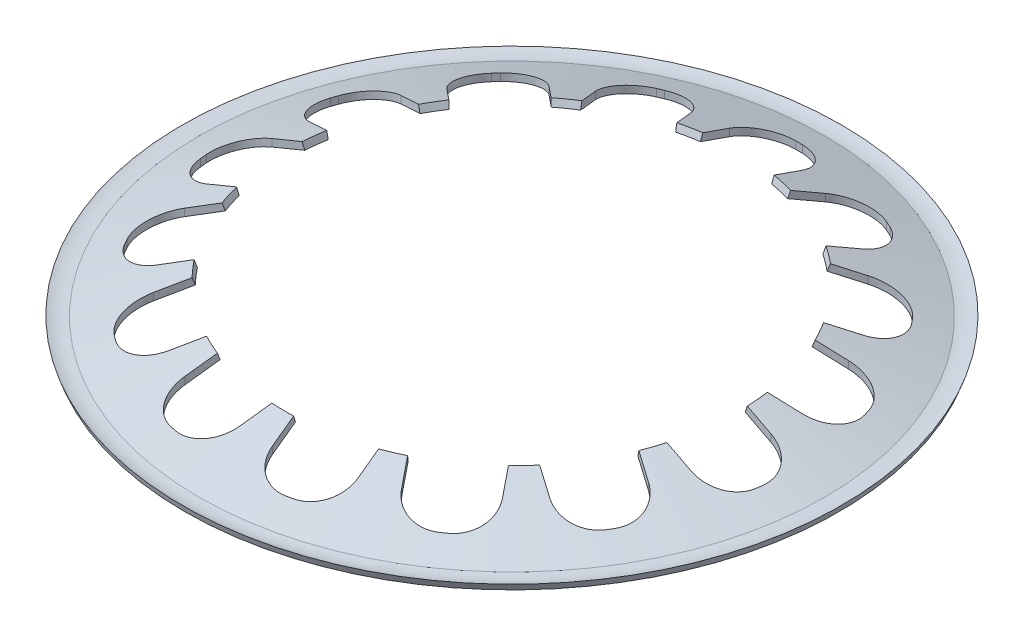
SolidWorks part; units mm, degrees
ref_plane "Plano frontal" through (0, 0, 0) normal (0, 0, 1) x (1, 0, 0)
ref_plane "Plano superior" through (0, 0, 0) normal (0, 1, 0) x (1, 0, 0)
ref_plane "Plano direito" through (0, 0, 0) normal (1, 0, 0) x (0, 0, -1)
sketch "Esboço1" plane through (0, 0, 0) normal (0, 0, 1) x (1, 0, 0)
  line L0 (0, -72.5644) -> (0, 61.8053) construction
  line L1 (40.25, 8.8426) -> (56.25, 3.1611)
  line L2 (58.8317, 3.5206) -> (59.25, 4.6985)
  line L3 (56.25, 4.4875) -> (40.6683, 10.0206)
  line L4 (40.6683, 10.0206) -> (40.25, 8.8426)
  arc A0 (56.25, 3.1611) -> (58.8317, 3.5206) centre (57.0193, 7.0864) ccw
  arc A1 (59.25, 4.6985) -> (56.25, 4.4875) centre (57.2704, 11.4128) cw
  point P13 (44.8894, 9.9657)
  dimension "D6" = 7
  dimension "D7" = 4
  dimension "D1" = 59.25
  dimension "D2" = 19
  dimension "D3" = 1.25
  dimension "D4" = 1.25
  dimension "D5" = 6.5
  dimension "D8" = 16
revolve "Revolução1" add sketch "Esboço1" angle 360 about L0
sketch "Esboço2" plane through (0, 0, 0) normal (0, 1, 0) x (1, 0, 0)
  line L0 (0, 0) -> (0, 25.5375) construction
  line L1 (-5.9196, 20.5713) -> (7.0804, 20.5713)
  line L2 (-5.9196, 20.5713) -> (-5.9196, 44.9999)
  line L3 (7.0804, 20.5713) -> (7.0804, 44.987)
  line L4 (2.9592, 21.2006) -> (14.8353, 15.913)
  line L5 (2.9592, 21.2006) -> (12.8953, 43.5172)
  line L6 (14.8353, 15.913) -> (24.7661, 38.2179)
  line L7 (0, 0) -> (10.387, 23.3297) construction
  line L8 (11.3265, 18.1641) -> (20.0252, 8.5032)
  line L9 (11.3265, 18.1641) -> (29.4804, 34.51)
  line L10 (20.0252, 8.5032) -> (38.1696, 24.8405)
  line L11 (0, 0) -> (18.9781, 17.0879) construction
  line L12 (17.7352, 11.9868) -> (21.7524, -0.3769)
  line L13 (17.7352, 11.9868) -> (40.9682, 19.5357)
  line L14 (21.7524, -0.3769) -> (44.9732, 7.1679)
  line L15 (0, 0) -> (24.2876, 7.8915) construction
  line L16 (21.0774, 3.7369) -> (19.7185, -9.1919)
  line L17 (21.0774, 3.7369) -> (45.3722, 1.1834)
  line L18 (19.7185, -9.1919) -> (44.0005, -11.744)
  line L19 (0, 0) -> (25.3976, -2.6694) construction
  line L20 (20.7751, -5.1591) -> (14.2751, -16.4174)
  line L21 (20.7751, -5.1591) -> (41.9309, -17.3734)
  line L22 (14.2751, -16.4174) -> (35.4197, -28.6253)
  line L23 (0, 0) -> (22.1161, -12.7688) construction
  line L24 (16.8806, -13.1631) -> (6.3634, -20.8043)
  line L25 (16.8806, -13.1631) -> (31.2394, -32.9262)
  line L26 (6.3634, -20.8043) -> (20.7146, -40.557)
  line L27 (0, 0) -> (15.0106, -20.6603) construction
  line L28 (10.0673, -18.891) -> (-2.6486, -21.5939)
  line L29 (10.0673, -18.891) -> (15.1463, -42.7858)
  line L30 (-2.6486, -21.5939) -> (2.4277, -45.476)
  line L31 (0, 0) -> (5.3096, -24.9795) construction
  line L32 (1.5133, -21.3526) -> (-11.2027, -18.6497)
  line L33 (1.5133, -21.3526) -> (-3.5657, -45.2473)
  line L34 (-11.2027, -18.6497) -> (-16.279, -42.5319)
  line L35 (0, 0) -> (-5.3096, -24.9795) construction
  line L36 (-7.3024, -20.122) -> (-17.8197, -12.4808)
  line L37 (-7.3024, -20.122) -> (-21.6612, -39.8852)
  line L38 (-17.8197, -12.4808) -> (-32.1708, -32.2335)
  line L39 (0, 0) -> (-15.0106, -20.6603) construction
  line L40 (-14.8555, -15.4122) -> (-21.3555, -4.1539)
  line L41 (-14.8555, -15.4122) -> (-36.0113, -27.6265)
  line L42 (-21.3555, -4.1539) -> (-42.5001, -16.3617)
  line L43 (0, 0) -> (-22.1161, -12.7688) construction
  line L44 (-19.8399, -8.0375) -> (-21.1987, 4.8913)
  line L45 (-19.8399, -8.0375) -> (-44.1346, -10.591)
  line L46 (-21.1987, 4.8913) -> (-50.9695, 1.7622)
  line L47 (0, 0) -> (-25.3976, -2.6694) construction
  line L48 (-21.3938, 0.727) -> (-17.3765, 13.0907)
  line L49 (-21.3938, 0.727) -> (-44.6267, 8.2758)
  line L50 (-17.3765, 13.0907) -> (-40.5973, 20.6356)
  line L51 (0, 0) -> (-24.2876, 7.8915) construction
  line L52 (-19.2485, 9.3658) -> (-10.5498, 19.0266)
  line L53 (-19.2485, 9.3658) -> (-37.4025, 25.7117)
  line L54 (-10.5498, 19.0266) -> (-28.6942, 35.3639)
  line L55 (0, 0) -> (-18.9781, 17.0879) construction
  line L56 (-13.775, 16.3851) -> (-1.8989, 21.6727)
  line L57 (-13.775, 16.3851) -> (-23.711, 38.7017)
  line L58 (-1.8989, 21.6727) -> (-11.8296, 43.9775)
  line L59 (0, 0) -> (-10.387, 23.3297) construction
  arc A0 (20.8267, 46.5537) -> (21.8561, 46.0794) centre (0, 0) cw
  arc A1 (0.0911, 50.9999) -> (1.2244, 50.9853) centre (0, 0) cw
  arc A2 (37.9613, 34.0579) -> (38.7087, 33.2059) centre (0, 0) cw
  arc A3 (48.5319, 15.6732) -> (48.8683, 14.5908) centre (0, 0) cw
  arc A4 (50.711, -5.4215) -> (50.578, -6.5471) centre (0, 0) cw
  arc A5 (44.1217, -25.5788) -> (43.5424, -26.553) centre (0, 0) cw
  arc A6 (29.9033, -41.3133) -> (28.9778, -41.9677) centre (0, 0) cw
  arc A7 (10.5144, -49.9044) -> (9.4028, -50.1257) centre (0, 0) cw
  arc A8 (-10.6926, -49.8665) -> (-11.7981, -49.6166) centre (0, 0) cw
  arc A9 (-30.0507, -41.2063) -> (-30.959, -40.5283) centre (0, 0) cw
  arc A10 (-44.2128, -25.4211) -> (-44.7668, -24.4323) centre (0, 0) cw
  arc A11 (-50.7301, -5.2404) -> (-50.9695, 1.7622) centre (0, 0) cw
  arc A12 (-48.4757, 15.8465) -> (-48.1115, 16.9198) centre (0, 0) cw
  arc A13 (-37.8394, 34.1933) -> (-37.0702, 35.0257) centre (0, 0) cw
  arc A14 (-20.6603, 46.6278) -> (-19.619, 47.0754) centre (0, 0) cw
  arc A15 (-16.279, -42.5319) -> (-11.7981, -49.6166) centre (-10.4101, -43.7793) ccw
  arc A16 (-3.5657, -45.2473) -> (-10.6926, -49.8665) centre (-9.4346, -43.9999) cw
  arc A17 (15.1463, -42.7858) -> (10.5144, -49.9044) centre (9.2774, -44.0333) cw
  arc A18 (2.4277, -45.476) -> (9.4028, -50.1257) centre (8.2966, -44.2286) ccw
  arc A19 (31.2394, -32.9262) -> (29.9033, -41.3133) centre (26.3853, -36.4529) cw
  arc A20 (20.7146, -40.557) -> (28.9778, -41.9677) centre (25.5687, -37.0303) ccw
  arc A21 (41.9309, -17.3734) -> (44.1217, -25.5788) centre (38.9309, -22.5696) cw
  arc A22 (35.4197, -28.6253) -> (43.5424, -26.553) centre (38.4197, -23.4291) ccw
  arc A23 (44.0005, -11.744) -> (50.578, -6.5471) centre (44.6277, -5.7769) ccw
  arc A24 (45.3722, 1.1834) -> (50.711, -5.4215) centre (44.745, -4.7837) cw
  arc A25 (44.9732, 7.1679) -> (48.8683, 14.5908) centre (43.1191, 12.8743) ccw
  arc A26 (40.9682, 19.5357) -> (48.5319, 15.6732) centre (42.8223, 13.8293) cw
  arc A27 (38.1696, 24.8405) -> (38.7087, 33.2059) centre (34.1548, 29.2993) ccw
  arc A28 (29.4804, 34.51) -> (37.9613, 34.0579) centre (33.4952, 30.0511) cw
  arc A29 (24.7661, 38.2179) -> (21.8561, 46.0794) centre (19.2848, 40.6583) ccw
  arc A30 (12.8953, 43.5172) -> (20.8267, 46.5537) centre (18.3765, 41.0768) cw
  arc A31 (7.0804, 44.987) -> (1.2244, 50.9853) centre (1.0804, 44.987) ccw
  arc A32 (-5.9196, 44.9999) -> (0.0911, 50.9999) centre (0.0804, 44.9999) cw
  arc A33 (-11.8296, 43.9775) -> (-19.619, 47.0754) centre (-17.3109, 41.5371) ccw
  arc A34 (-23.711, 38.7017) -> (-20.6603, 46.6278) centre (-18.2297, 41.1422) cw
  arc A35 (-28.6942, 35.3639) -> (-37.0702, 35.0257) centre (-32.709, 30.9051) ccw
  arc A36 (-37.4025, 25.7117) -> (-37.8394, 34.1933) centre (-33.3877, 30.1705) cw
  arc A37 (-40.5973, 20.6356) -> (-48.1115, 16.9198) centre (-42.4514, 14.9292) ccw
  arc A38 (-44.6267, 8.2758) -> (-48.4757, 15.8465) centre (-42.7726, 13.9822) cw
  arc A39 (-44.1346, -10.591) -> (-50.7301, -5.2404) centre (-44.7618, -4.6239) cw
  arc A40 (-42.5001, -16.3617) -> (-44.7668, -24.4323) centre (-39.5001, -21.5579) ccw
  arc A41 (-36.0113, -27.6265) -> (-44.2128, -25.4211) centre (-39.0113, -22.4304) cw
  arc A42 (-32.1708, -32.2335) -> (-30.959, -40.5283) centre (-27.3167, -35.7603) ccw
  arc A43 (-21.6612, -39.8852) -> (-30.0507, -41.2063) centre (-26.5153, -36.3585) cw
  point P80 (0, 0)
  dimension "D2" = 15
  dimension "D3" = 6
  dimension "D1" = 13
extrude "Corte-extrusão2" cut sketch "Esboço2" along normal through all contours A7 L29 L26 L24 L28 L32 L33 L30 | A6 L25 L22 L20 L24 L28 L29 L26 | A5 L21 L18 L16 L20 L24 L25 L22 | A4 L17 L14 L12 L16 L20 L21 L18 | A3 L13 L10 L8 L12 L16 L17 L14 | A2 L9 L6 L4 L8 L12 L13 L10 | A0 L5 L3 L1 L4 L8 L9 L6 | A1 L2 L58 L56 L1 L4 L5 L3 | A14 L57 L54 L52 L56 L1 L2 L58 | A13 L53 L50 L48 L52 L56 L57 L54 | A12 L49 L46 L44 L48 L52 L53 L50 | A11 L45 L42 L40 L44 L48 L49 L46 | A10 L41 L38 L36 L40 L44 L45 L42 | A9 L37 L34 L32 L36 L40 L41 L38 | A8 L33 L30 L28 L32 L36 L37 L34 region at (-14.3629, 0, -33.6921) region at (0.5826, 0, -36.6211) region at (15.4274, 0, -33.2181) region at (-26.825, 0, -24.9373) region at (27.6047, 0, -24.0714) region at (-34.6487, 0, -11.8707) region at (35.0088, 0, -10.7624) region at (-36.7382, 0, 3.1744) region at (36.3596, 0, 4.4074) region at (-32.0062, 0, 17.806) region at (31.4235, 0, 18.8151) region at (-21.9967, 0, 29.2847) region at (21.054, 0, 29.9696) region at (-8.1839, 0, 35.6998) region at (7.0441, 0, 35.942)
fillet "Filete1" radius 6 1 edges at (-50.9695, 5.6886, -1.7622)
